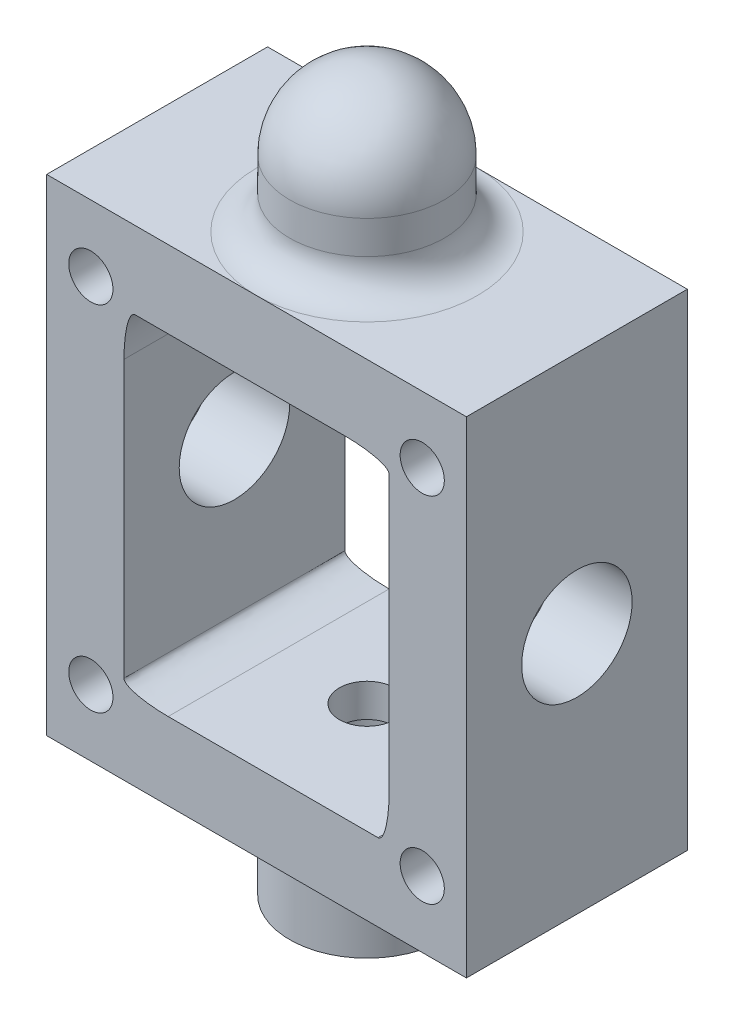
SolidWorks part; units mm, degrees
ref_plane "Front Plane" through (0, 0, 0) normal (0, 0, 1) x (1, 0, 0)
ref_plane "Top Plane" through (0, 0, 0) normal (0, 1, 0) x (1, 0, 0)
ref_plane "Right Plane" through (0, 0, 0) normal (1, 0, 0) x (0, 0, -1)
sketch "Sketch1" plane through (0, 0, 0) normal (0, 0, 1) x (1, 0, 0)
  line L1 (-19, -22) -> (19, -22)
  line L2 (-19, -22) -> (-19, 22)
  line L3 (-19, 22) -> (19, 22)
  line L4 (19, -22) -> (19, 22)
  circle A0 centre (-15, 16) radius 2
  circle A1 centre (15, 16) radius 2
  circle A2 centre (15, -16) radius 2
  circle A3 centre (-15, -16) radius 2
  point P0 (0, 0)
  dimension "D3" = 4
  dimension "D4" = 6
  dimension "D8" = 4
  dimension "D9" = 6
  dimension "D10" = 6
  dimension "D1" = 38
  dimension "D2" = 44
  dimension "D5" = 4
  dimension "D6" = 4
  dimension "D7" = 4
  dimension "D11" = 6
  dimension "D12" = 15
  dimension "D13" = 16
extrude "Boss-Extrude1" add sketch "Sketch1" along normal mid plane 20
sketch "Sketch2" plane through (0, 22, 0) normal (0, 1, 0) x (1, 0, 0)
  circle A0 centre (0, 0) radius 7
  dimension "D1" = 14
extrude "Boss-Extrude2" add sketch "Sketch2" along normal blind 13
fillet "Fillet1" radius 3 1 edges at (0, 22, 7)
fillet "Fillet2" radius 7 1 edges at (0, 35, 7)
sketch "Sketch3" plane through (0, 0, 0) normal (0, 0, 1) x (1, 0, 0)
  line L1 (-12, -15) -> (12, -15)
  line L2 (-12, -15) -> (-12, 15)
  line L3 (-12, 15) -> (12, 15)
  line L4 (12, -15) -> (12, 15)
  line L5 (-12, -15) -> (12, 15) construction
  line L6 (-12, 15) -> (12, -15) construction
  point P0 (0, 0)
  dimension "D1" = 12
  dimension "D2" = 15
extrude "Cut-Extrude1" cut sketch "Sketch3" against normal through all both and the other way through all
sketch "Sketch4" plane through (0, -22, 0) normal (0, -1, 0) x (1, 0, 0)
  circle A0 centre (0, 0) radius 7
  dimension "D1" = 14
extrude "Boss-Extrude3" add sketch "Sketch4" along normal blind 8
sketch "Sketch7" plane through (0, 0, 0) normal (1, 0, 0) x (0, 0, -1)
  line L0 (0, -30) -> (0, -12.56)
  line L1 (-7, -30) -> (7, -30) construction
  line L4 (0, -30) -> (5, -30)
  line L5 (5, -18) -> (5, -30)
  line L6 (2.5, -18) -> (5, -18)
  line L11 (0, -12.56) -> (2.5, -12.56)
  line L12 (2.5, -18) -> (2.5, -12.56)
  line L18 (0, -30) -> (0, -35.6345) construction
  point P4 (0, 0)
revolve "Cut-Revolve1" cut sketch "Sketch7" angle 360 about L18
sketch "Sketch8" plane through (0, 0, 0) normal (1, 0, 0) x (0, 0, -1)
  circle A0 centre (0, 0) radius 5
  dimension "D1" = 10
extrude "Cut-Extrude2" cut sketch "Sketch8" against normal through all both and the other way through all
sketch "Sketch9" plane through (0, 15, 0) normal (0, -1, 0) x (1, 0, 0)
  circle A0 centre (0, 0) radius 1.75
  dimension "D1" = 3.5
extrude "Cut-Extrude3" cut sketch "Sketch9" against normal blind 13 and the other way through all
fillet "Fillet3" radius 1 4 edges at (12, -15, 0) (12, 15, 0) (-12, -15, 0) (-12, 15, 0)
